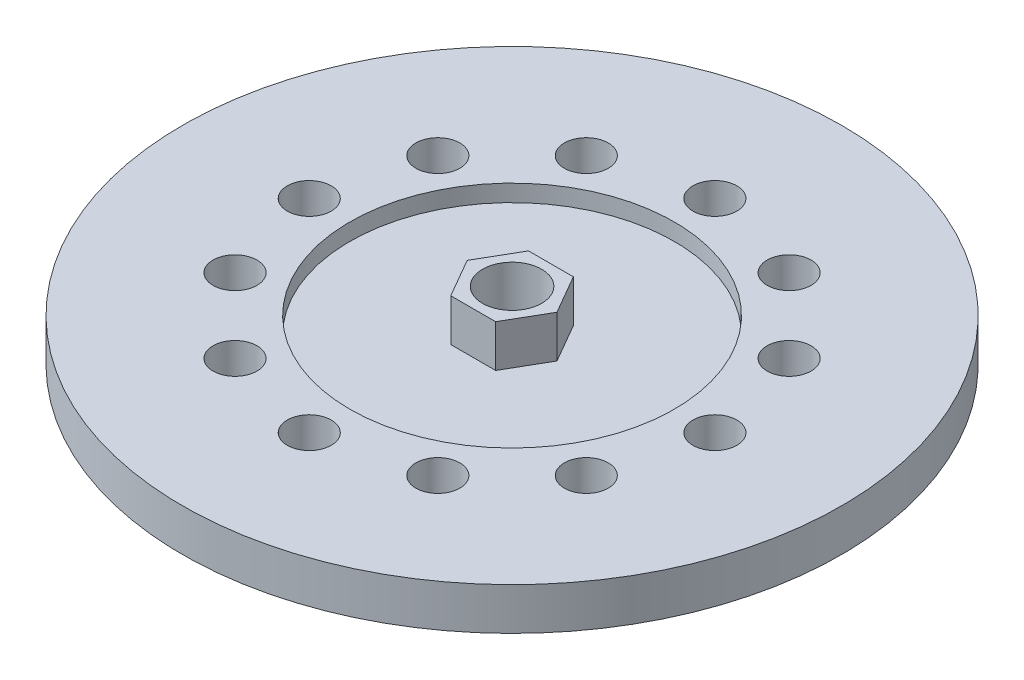
SolidWorks part; units mm, degrees
ref_plane "Front Plane" through (0, 0, 0) normal (0, 0, 1) x (1, 0, 0)
ref_plane "Top Plane" through (0, 0, 0) normal (0, 1, 0) x (1, 0, 0)
ref_plane "Right Plane" through (0, 0, 0) normal (1, 0, 0) x (0, 0, -1)
sketch "Sketch1" plane through (0, 0, 0) normal (0, 1, 0) x (1, 0, 0)
  circle A0 centre (0, 0) radius 49.53
  dimension "D1" = 99.06
extrude "Boss-Extrude1" add sketch "Sketch1" along normal blind 3.81
sketch "Sketch4" plane through (0, 3.81, 0) normal (0, 1, 0) x (1, 0, 0)
  line L0 (-3.3729, 5.842) -> (3.3729, 5.842)
  line L1 (3.3729, 5.842) -> (6.7458, 0)
  line L2 (6.7458, 0) -> (3.3729, -5.842)
  line L3 (3.3729, -5.842) -> (-3.3729, -5.842)
  line L4 (-3.3729, -5.842) -> (-6.7458, 0)
  line L5 (-6.7458, 0) -> (-3.3729, 5.842)
  circle A0 centre (0, 0) radius 4.445
  point P6 (0, 5.842)
  dimension "D3" = 8.89
  dimension "D1" = 120
  dimension "D2" = 11.684
extrude "Boss-Extrude2" add sketch "Sketch4" along normal blind 6.35 contours L5 L4 L3 L2 L1 L0 A0 region at (0, 3.81, -5.6635)
sketch "Sketch5" plane through (0, 3.81, 0) normal (0, 1, 0) x (1, 0, 0)
  circle A0 centre (0, 30.48) radius 3.302
  circle A1 centre (15.24, 26.3965) radius 3.302
  circle A2 centre (26.3965, 15.24) radius 3.302
  circle A3 centre (30.48, 0) radius 3.302
  circle A4 centre (26.3965, -15.24) radius 3.302
  circle A5 centre (15.24, -26.3965) radius 3.302
  circle A6 centre (0, -30.48) radius 3.302
  circle A7 centre (-15.24, -26.3965) radius 3.302
  circle A8 centre (-26.3965, -15.24) radius 3.302
  circle A9 centre (-30.48, 0) radius 3.302
  circle A10 centre (-26.3965, 15.24) radius 3.302
  circle A11 centre (-15.24, 26.3965) radius 3.302
  point P28 (0, 0)
  dimension "D2" = 6.604
  dimension "D1" = 30.48
extrude "Cut-Extrude1" cut sketch "Sketch5" against normal through all
sketch "Sketch6" plane through (0, 0, 0) normal (0, -1, 0) x (1, 0, 0)
  circle A0 centre (0, 0) radius 3.2639
  circle A1 centre (0, 0) radius 9.525
  dimension "D1" = 6.5278
  dimension "D2" = 19.05
extrude "Boss-Extrude3" add sketch "Sketch6" along normal blind 16.51 contours A1 A0 region at (-9.2556, 0, 0)
sketch "Sketch7" plane through (0, 0, 0) normal (0, -1, 0) x (1, 0, 0)
  line L2 (-3.2639, 0) -> (-3.2639, 20.32)
  line L3 (-3.2639, 20.32) -> (3.2639, 20.32)
  line L4 (3.2639, 0) -> (3.2639, 20.32)
  circle A0 centre (0, 0) radius 3.2639 construction
  arc A1 (3.2639, 0) -> (-3.2639, 0) centre (0, 0) ccw
  circle A2 centre (0, 0) radius 3.2639 construction
  dimension "D1" = 20.32
extrude "Boss-Extrude4" add sketch "Sketch7" along normal up to surface (16.51 mm away) up to face at (0, -16.51, -3.2639)
chamfer "Chamfer1" distance 10.16 angle 61 1 edges at (0, -16.51, 20.32) first distance on face at (0, -16.51, -3.2639)
pattern_circular "CirPattern1" count 4 over 360 about axis through (0, -16.51, 0) along (0, 1, 0) of "Boss-Extrude4", "Chamfer1" reverse direction yes
sketch "Sketch8" plane through (0, 3.81, 0) normal (0, 1, 0) x (1, 0, 0)
  circle A0 centre (0, 0) radius 49.53
  circle A1 centre (0, 0) radius 24.384
  circle A2 centre (0, 0) radius 49.53 construction
  circle A4 centre (0, 30.48) radius 3.302
  circle A5 centre (0, 30.48) radius 3.302 construction
  circle A6 centre (15.24, 26.3965) radius 3.302
  circle A7 centre (26.3965, 15.24) radius 3.302
  circle A8 centre (30.48, 0) radius 3.302
  circle A9 centre (26.3965, -15.24) radius 3.302
  circle A10 centre (15.24, -26.3965) radius 3.302
  circle A11 centre (0, -30.48) radius 3.302
  circle A12 centre (-15.24, -26.3965) radius 3.302
  circle A13 centre (-26.3965, -15.24) radius 3.302
  circle A14 centre (-30.48, 0) radius 3.302
  circle A15 centre (-26.3965, 15.24) radius 3.302
  circle A16 centre (-15.24, 26.3965) radius 3.302
  point P36 (0, 0)
  dimension "D1" = 25.146
  dimension "D2" = 12
extrude "Boss-Extrude5" add sketch "Sketch8" along normal blind 2.54
